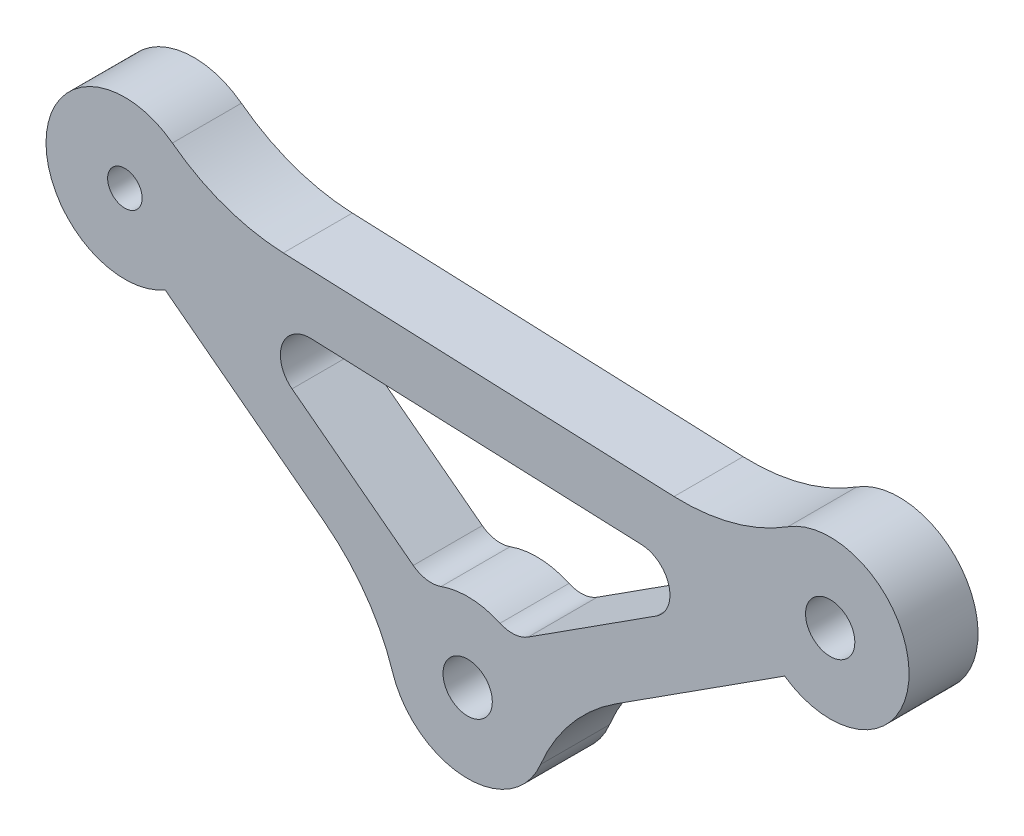
SolidWorks part; units mm, degrees
ref_plane "Front Plane" through (0, 0, 0) normal (0, 0, 1) x (1, 0, 0)
ref_plane "Top Plane" through (0, 0, 0) normal (0, 1, 0) x (1, 0, 0)
ref_plane "Right Plane" through (0, 0, 0) normal (1, 0, 0) x (0, 0, -1)
sketch "Sketch1" plane through (0, 0, 0) normal (0, 0, 1) x (1, 0, 0)
  line L0 (0, 0) -> (0, 28420.5788) construction
  line L1 (0, 0) -> (-28420.5788, 0) construction
  line L2 (-23, 10) -> (-28, 10)
  line L3 (-23, 0) -> (23, 0)
  line L4 (-23, 0) -> (-23, 10)
  line L5 (-23, 10) -> (23, 10)
  line L6 (23, 0) -> (23, 10)
  line L7 (-28, 10) -> (-41.8608, 50.4677)
  line L8 (-24.6313, 80.3256) -> (15.2446, 88.1625)
  line L9 (23, 10) -> (28, 10)
  line L10 (28, 10) -> (39.4051, 19.57)
  line L11 (39.4051, 19.57) -> (39.4051, 38.57)
  line L12 (39.4051, 38.57) -> (22.9346, 83.8223)
  line L13 (-20.22, 57.88) -> (-41.0516, 204.4066) construction
  line L14 (16.5541, 81.5) -> (-4.2776, 228.0266) construction
  line L15 (-75.8246, 230.8844) -> (-41.0516, 204.4066) construction
  line L16 (-41.0516, 204.4066) -> (-4.2776, 228.0266) construction
  line L17 (-4.2776, 228.0266) -> (-75.8246, 230.8844) construction
  line L18 (-75.8246, 230.8844) -> (-226.1828, 176.1814) construction
  line L19 (-204.7956, 140.0346) -> (9.2044, 224.1635) construction
  line L20 (-226.1828, 176.1814) -> (-204.7956, 140.0346) construction
  line L21 (-204.7956, 140.0346) -> (-256.0612, 159.9555) construction
  line L22 (-256.0612, 159.9555) -> (-226.1828, 176.1814) construction
  line L23 (-20.22, 57.88) -> (33.1708, 65.9687)
  line L24 (33.1708, 65.9687) -> (9.2044, 224.1635)
  circle A0 centre (-20.22, 57.88) radius 22.875 construction
  circle A1 centre (16.5541, 81.5) radius 6.79 construction
  arc A2 (-41.8608, 50.4677) -> (-24.6313, 80.3256) centre (-20.22, 57.88) cw
  arc A3 (15.2446, 88.1625) -> (22.9346, 83.8223) centre (16.5541, 81.5) cw
  circle A4 centre (-20.22, 57.88) radius 17.5 construction
  circle A5 centre (16.5541, 81.5) radius 7.5 construction
  circle A6 centre (-41.0516, 204.4066) radius 13.1881 construction
  circle A7 centre (-4.2776, 228.0266) radius 8.7345 construction
  circle A8 centre (-75.8246, 230.8844) radius 8.7345 construction
  circle A9 centre (-226.1828, 176.1814) radius 8.1525 construction
  circle A10 centre (-204.7956, 140.0346) radius 9.1166 construction
  dimension "D7" = 45.75
  dimension "D8" = 13.58
  dimension "D14" = 35
  dimension "D15" = 15
  dimension "D1" = 46
  dimension "D2" = 10
  dimension "D3" = 57.88
  dimension "D4" = 20.22
  dimension "D5" = 16.5541
  dimension "D6" = 81.5
  dimension "D9" = 5
  dimension "D10" = 5
  dimension "D11" = 140
  dimension "D12" = 19
  dimension "D13" = 160
  dimension "D16" = 148
  dimension "D17" = 110
  dimension "D18" = 160
  dimension "D19" = 54
  dimension "D20" = 214
  dimension "D21" = 42
  dimension "D22" = 34
  dimension "D23" = 55
  dimension "D24" = 54
  dimension "D25" = 160
sketch "Sketch2" plane through (0, 0, 0) normal (0, 0, 1) x (1, 0, 0)
  line L0 (-4.2776, 228.0266) -> (-75.8246, 230.8844) construction
  line L1 (-75.8246, 230.8844) -> (-41.0516, 204.4066) construction
  line L2 (-41.0516, 204.4066) -> (-4.2776, 228.0266) construction
  line L3 (-4.2776, 228.0266) -> (-6.7756, 228.1264)
  line L4 (-75.8246, 230.8844) -> (-74.4323, 229.8242)
  line L5 (-34.3205, 208.73) -> (-11.0087, 223.7032)
  line L6 (-74.076, 230.8145) -> (-75.8246, 230.8844)
  line L7 (-69.4598, 226.0379) -> (-47.4165, 209.2531)
  line L8 (-6.381, 226.6755) -> (-4.2776, 228.0266)
  line L9 (-12.2712, 228.3459) -> (-67.831, 230.5651)
  line L10 (-11.5681, 231.3202) -> (-68.2946, 233.586)
  line L11 (-13.9045, 225.4087) -> (-66.4371, 227.507)
  line L12 (-12.1514, 231.3435) -> (-67.7113, 233.5627) construction
  line L13 (-12.3909, 225.3483) -> (-67.9507, 227.5675) construction
  line L14 (-71.7417, 224.0047) -> (-48.7694, 206.5126)
  line L15 (-68.1068, 228.7784) -> (-45.1346, 211.2862)
  line L16 (-33.1904, 205.8903) -> (-8.8962, 221.4945)
  line L17 (-36.433, 210.9387) -> (-12.1388, 226.5429)
  line L18 (-67.6423, 228.4247) -> (-45.599, 211.6399) construction
  line L19 (-71.2772, 223.6511) -> (-49.2339, 206.8663) construction
  line L20 (-35.9418, 211.2542) -> (-12.63, 226.2274) construction
  line L21 (-32.6992, 206.2058) -> (-9.3874, 221.179) construction
  circle A0 centre (-75.8246, 230.8844) radius 8
  circle A1 centre (-41.0516, 204.4066) radius 8
  circle A2 centre (-4.2776, 228.0266) radius 8
  circle A3 centre (-41.0516, 204.4066) radius 2.5
  circle A4 centre (-75.8246, 230.8844) radius 1.75
  circle A5 centre (-4.2776, 228.0266) radius 2.5
  dimension "D1" = 16
  dimension "D2" = 3.5
  dimension "D3" = 5
  dimension "D4" = 5
  dimension "D5" = 3
  dimension "D6" = 3
  dimension "D7" = 3
  dimension "D8" = 3
  dimension "D9" = 3
  dimension "D10" = 3
extrude "Boss-Extrude2" add sketch "Sketch2" along normal blind 7 contours A0 A4 | A2 A5 | A1 A3 region at (-33.8288, 207.281, 0) region at (-11.5004, 225.1522, 0) region at (-68.1419, 229.6984, 0)
extrude "Boss-Extrude3" add sketch "Sketch2<6>" along normal blind 7 contours A2 L9 A0 L15 L11 L17 | A2 L10 A0 L9 | A2 L5 A1 L16 | A2 L17 A1 L5 | A1 L15 A0 L7 | A1 L7 A0 L14 region at (-23.4808, 217.4874, 0) region at (-21.8484, 214.9458, 0) region at (-40.1105, 227.968, 0) region at (-57.5231, 218.8471, 0) region at (-39.991, 230.9595, 0) region at (-59.3531, 216.4439, 0)
sketch "Sketch2<6>" plane through (0, 0, 0) normal (0, 0, 1) x (1, 0, 0) same geometry as "Sketch2"
fillet "Fillet4" radius 3 4 edges at (-45.1346, 211.2862, 3.5) (-36.433, 210.9387, 3.5) (-13.9045, 225.4087, 3.5) (-66.4371, 227.507, 3.5)
fillet "Fillet5" radius 20 2 edges at (-11.5681, 231.3202, 3.5) (-68.2946, 233.586, 3.5)
fillet "Fillet6" radius 20 2 edges at (-33.1904, 205.8903, 3.5) (-48.7694, 206.5126, 3.5)
